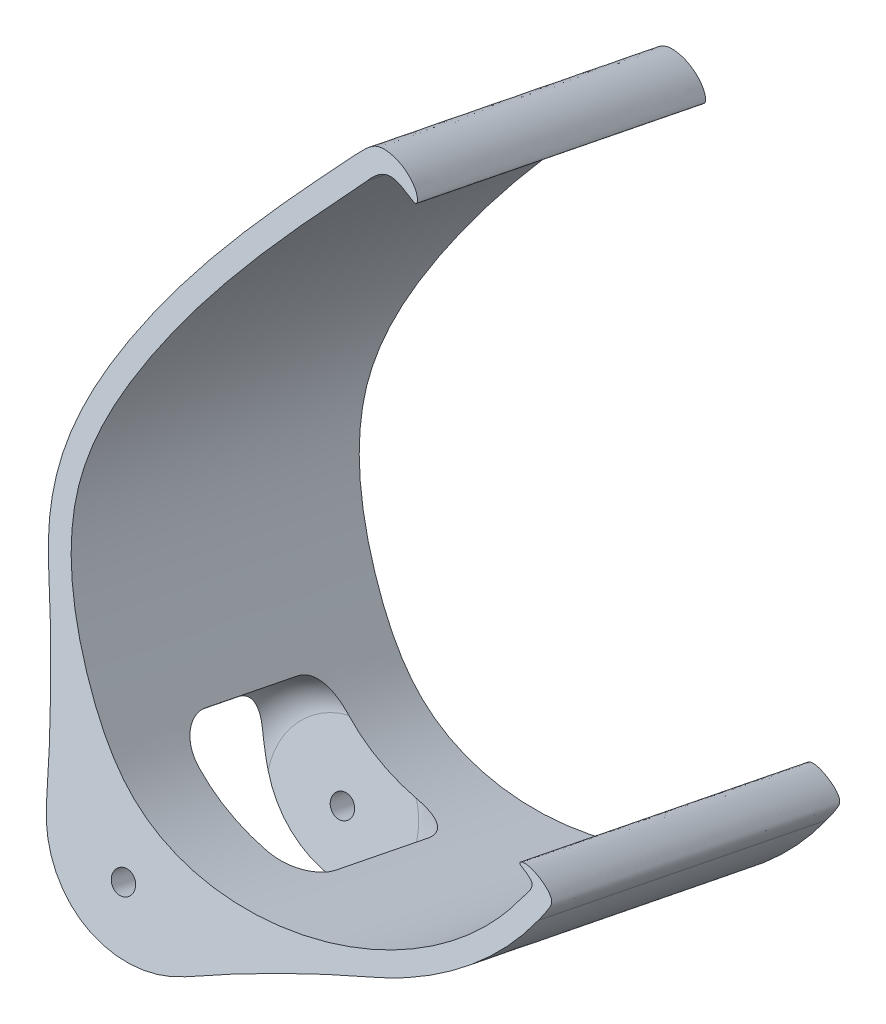
SolidWorks part; units mm, degrees
ref_plane "前视基准面" through (0, 0, 0) normal (0, 0, 1) x (1, 0, 0)
ref_plane "上视基准面" through (0, 0, 0) normal (0, 1, 0) x (1, 0, 0)
ref_plane "右视基准面" through (0, 0, 0) normal (1, 0, 0) x (0, 0, -1)
sketch "草图1" plane through (0, 0, 0) normal (0, 1, 0) x (1, 0, 0)
  line L0 (0, 0) -> (222.6675, 24.1899) construction
ref_axis "基准轴1" through (0, 0, 0) along (0.9942, 0, -0.108)
ref_plane "基准面1" through (0, 0, 0) normal (0.1039, 0.2733, 0.9563) x (0.9942, 0, -0.108)
ref_plane "基准面2" through (-27.5308, -72.4222, -253.4208) normal (0.1039, 0.2733, 0.9563) x (0.9942, 0, -0.108)
ref_plane "基准面3" through (-22.3363, -58.7576, -205.6055) normal (0.1039, 0.2733, 0.9563) x (0.9942, 0, -0.108)
sketch "草图4" plane through (-22.3363, -58.7576, -205.6055) normal (0.1039, 0.2733, 0.9563) x (0.9942, 0, -0.108)
  line L0 (79.159, 272.6491) -> (87.4981, 282.7153) construction
  line L1 (112.1038, 213.2471) -> (114.9313, 217.1192) construction
  line L2 (114.8044, 216.9454) -> (-1.2855, 216.9454) construction
  line L3 (3.7014, 201.9454) -> (89.9835, 201.9454) construction
  line L4 (69.8108, 201.9454) -> (62.7688, 188.7012) construction
  arc A0 (57.0261, 209.791) -> (83.4642, 195.7338) centre (69.8108, 201.9454) ccw
  circle A1 centre (66.2898, 195.3233) radius 1.6
  spline S0 degree 3 poles (74.1484, 285.7795) (62.3556, 270.526) (54.7256, 258.5634) (45.6965, 233.4782) (51.7686, 214.4475) (67.3939, 198.0087) (94.0542, 192.0791) (111.3459, 203.1327) (118.5869, 210.5661) knots 0 0 0 0 0.234318 0.358087 0.509491 0.603672 0.801755 1 1 1 1 construction
  spline S1 degree 3 poles (80.0552, 281.5729) (71.497, 272.1071) (59.1912, 258.4855) (48.9719, 233.6637) (55.5206, 216.4899) (73.5043, 192.358) (106.2983, 197.7848) (115.7948, 213.1989) knots 0 0 0 0 0.26391 0.385656 0.53157 0.620527 1 1 1 1
  spline S2 degree 1 poles (77.8298, 283.5849) (118.349, 211.6253) knots 0 0 1 1 construction
  spline S3 degree 3 poles (77.8298, 283.5849) (75.8007, 281.3406) (71.7472, 276.8567) (65.8259, 269.9344) (60.2485, 262.6426) (56.0502, 256.1061) (53.0427, 250.5139) (51.0295, 246.0767) (49.4577, 241.4254) (48.5035, 236.5677) (48.4264, 231.5459) (49.4505, 225.0235) (51.7915, 218.7893) (54.5436, 213.6893) (56.2872, 210.8596) (58.1323, 208.1682) (60.6616, 205.0473) (64.2833, 201.7266) (68.5241, 199.081) (74.6718, 196.5135) (83.037, 194.9953) (93.3795, 195.638) (103.3044, 198.5934) (110.6119, 202.9332) (115.4578, 207.5231) (117.4748, 210.2064) (118.349, 211.6253) knots 0 0 0 0 0.0625 0.125 0.1875 0.25 0.28125 0.3125 0.34375 0.375 0.40625 0.4375 0.5 0.53125 0.548317 0.563942 0.59375 0.625 0.65625 0.6875 0.75 0.8125 0.875 0.9375 0.96875 1 1 1 1
  spline S4 degree 3 poles (77.8298, 283.5849) (78.616, 284.3547) (79.734, 285.9529) (84.1956, 285.4939) (87.0006, 282.6556) (86.571, 281.0168) (82.6505, 284.5272) (80.4169, 282.0636) (80.0552, 281.5729) knots 0 0 0 0 0.185673 0.241813 0.609549 0.679609 0.872351 1 1 1 1
  spline S5 degree 3 poles (118.349, 211.6253) (118.5722, 211.9225) (119.522, 213.4957) (120.0064, 215.0559) (115.7411, 217.445) (114.2945, 216.719) (117.4065, 215.6444) (116.6878, 214.3479) (115.7948, 213.1989) knots 0 0 0 0 0.111671 0.246985 0.601944 0.662863 0.856176 1 1 1 1
  dimension "D4" = 15
  dimension "D5" = 30
  dimension "D6" = 3.2
  dimension "D2" = 8
  dimension "D3" = 6
  dimension "D1" = 3
extrude "凸台-拉伸1" add sketch "草图4" along normal blind 50 contours S3 A0 | S3 S5 S1 S4 region at (39.5715, 132.6674, -267.0361) region at (23.7178, 180.9146, -279.1018)
fillet "圆角1" radius 200 2 edges
ref_plane "基准面4" through (-18.3885, -48.3726, -169.2659) normal (0.1039, 0.2733, 0.9563) x (0.9946, -0.0285, -0.0999)
sketch "草图6" plane through (-18.3885, -48.3726, -169.2659) normal (0.1039, 0.2733, 0.9563) x (0.9946, -0.0285, -0.0999)
  circle A1 centre (60.4641, 197.2045) radius 15
  dimension "D1" = 30
extrude "切除-拉伸1" cut sketch "草图6" against normal blind 26
fillet "圆角2" radius 5 4 edges at (53.9591, 131.5383, -255.7282) (29.7529, 143.958, -256.6478) (56.6602, 138.6439, -230.8643) (32.454, 151.0636, -231.7838)
